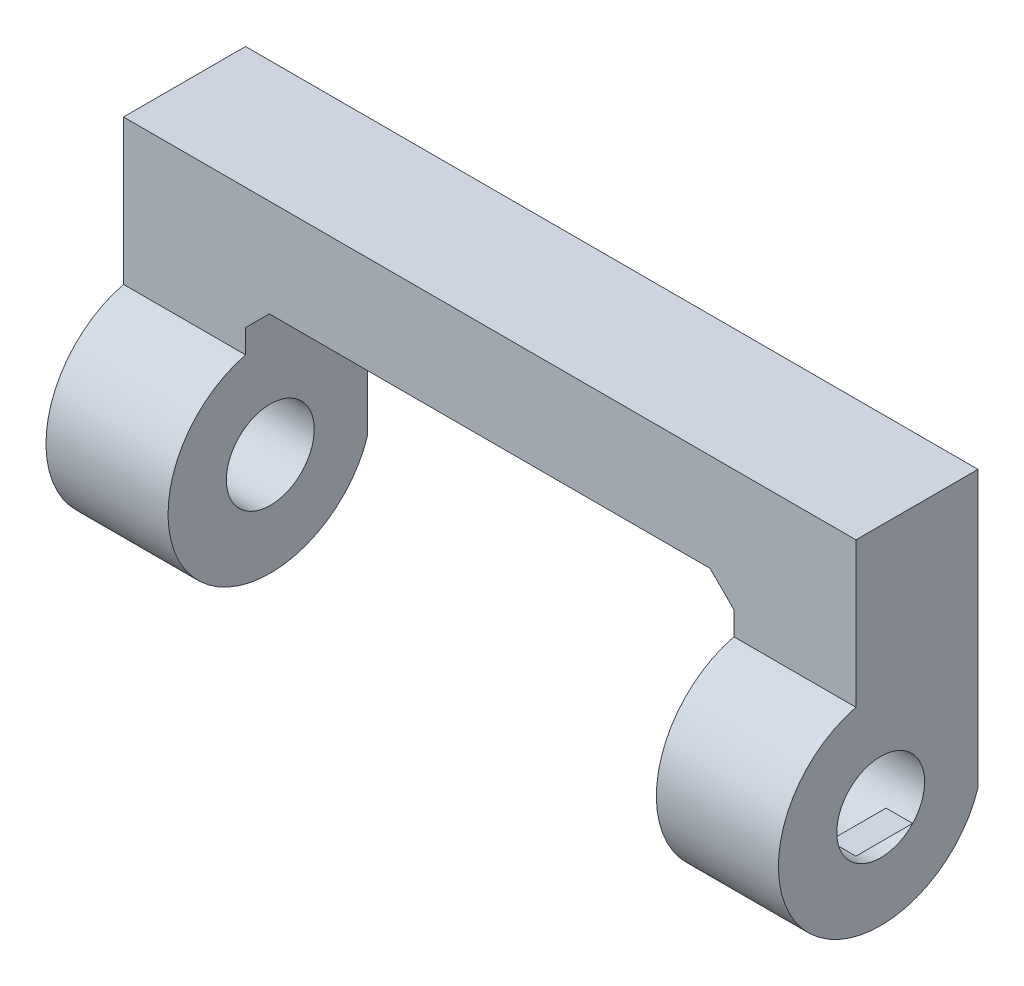
SolidWorks part; units mm, degrees
ref_plane "Front Plane" through (0, 0, 0) normal (0, 0, 1) x (1, 0, 0)
ref_plane "Top Plane" through (0, 0, 0) normal (0, 1, 0) x (1, 0, 0)
ref_plane "Right Plane" through (0, 0, 0) normal (1, 0, 0) x (0, 0, -1)
sketch "Model" plane through (0, 0, 0) normal (0, 0, 1) x (1, 0, 0)
  line L0 (289.64, 39.2394) -> (289.64, 28.0169)
  line L1 (319.644, 39.2394) -> (319.644, 28.0165)
  line L2 (289.64, 39.2394) -> (319.644, 39.2394)
  line L3 (314.644, 28.0181) -> (319.644, 28.0165)
  line L4 (314.644, 34.2647) -> (314.644, 28.0181)
  line L11 (313.6697, 35.2359) -> (314.644, 34.2647)
  line L12 (313.6697, 35.2359) -> (314.644, 34.2634)
  line L18 (313.6697, 35.2359) -> (313.6677, 35.2391)
  line L19 (314.644, 34.2647) -> (313.6677, 35.2391)
  line L21 (289.64, 28.0169) -> (294.64, 28.0201)
  line L24 (294.64, 28.0201) -> (294.64, 34.2666)
  line L32 (294.64, 34.2666) -> (295.6145, 35.2409)
  line L33 (295.6125, 35.2377) -> (295.6145, 35.2409)
  line L34 (295.6125, 35.2377) -> (294.64, 34.2666)
  line L36 (304.6401, 35.24) -> (313.6677, 35.2391)
  line L37 (304.6401, 35.24) -> (313.6697, 35.2359)
  line L44 (295.6145, 35.2409) -> (304.6401, 35.24)
  line L45 (295.6125, 35.2377) -> (304.6401, 35.24)
  line L48 (304.6401, 35.24) -> (304.6401, 35.2368)
  line L49 (295.6125, 35.2377) -> (304.6401, 35.2368)
  line L53 (304.6401, 35.2368) -> (313.6697, 35.2359)
  dimension "D1" = 5
  dimension "D2" = 5
extrude "Boss-Extrude1" add sketch "Model" along normal blind 5 contours L32 L44 L36 L19 L4 L3 L1 L2 L0 L21 L24 region at (304.642, 38.9191, 0)
sketch "Sketch2" plane through (289.64, 0, 0) normal (-1, 0, 0) x (0, 0, 1)
  line L0 (0, 30.5265) -> (0, 27.9427)
  arc A0 (0, 27.9427) -> (0, 30.5265) centre (3.9858, 29.2346) ccw
  circle A1 centre (3.9857, 29.252) radius 1.7997
  line M218 (0, 28.0169) -> (5, 28.0169)
  line M219 (5, 28.0169) -> (5, 39.2394)
extrude "Cut-Extrude1" cut sketch "Sketch2" against normal through all contours A1 M219 M218 region at (289.64, 29.443, 3.7016)
extrude "Boss-Extrude2" add sketch "Sketch2<3>" against normal blind 5
sketch "Sketch2<3>" plane through (289.64, 0, 0) normal (-1, 0, 0) x (0, 0, 1) same geometry as "Sketch2"
ref_plane "Plane1" through (304.642, 0, 0) normal (-1, 0, 0) x (0, 0, 1)
sketch "Sketch3" plane through (314.644, 0, 0) normal (-1, 0, 0) x (0, 0, 1)
  line L0 (0, 30.5265) -> (0, 27.9427)
  arc A0 (0, 27.9427) -> (0, 30.5265) centre (3.9858, 29.2346) ccw
  circle A1 centre (3.9857, 29.252) radius 1.7997
  point P0 (3.9858, 29.2346)
extrude "Boss-Extrude3" add sketch "Sketch3" against normal blind 5
